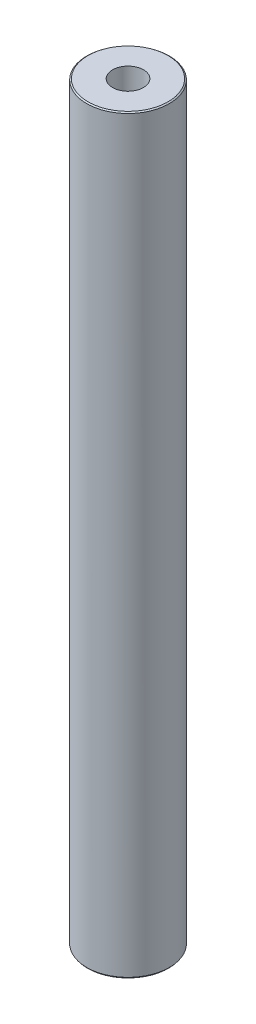
SolidWorks part; units mm, degrees
ref_plane "Front Plane" through (0, 0, 0) normal (0, 0, 1) x (1, 0, 0)
ref_plane "Top Plane" through (0, 0, 0) normal (0, 1, 0) x (1, 0, 0)
ref_plane "Right Plane" through (0, 0, 0) normal (1, 0, 0) x (0, 0, -1)
sketch "Sketch1" plane through (0, 0, 0) normal (0, 1, 0) x (1, 0, 0)
  circle A0 centre (0, 0) radius 30
  dimension "SHAFT_OD" = 60
extrude "Boss-Extrude1" add sketch "Sketch1" along normal blind 544.9537
sketch "Sketch2" plane through (0, 0, 0) normal (0, 1, 0) x (1, 0, 0)
  circle A0 centre (0, 0) radius 11.2205
  dimension "BORE_D" = 22.441
extrude "Cut-Extrude1" cut sketch "Sketch2" along normal through all
chamfer "Chamfer1" distance 0.7146 angle 51.955 2 edges at (0, 544.9537, 30) (0, 0, 30) first distance on face at (0, 544.9537, 30) first distance on face at (0, 0, 11.2205)
